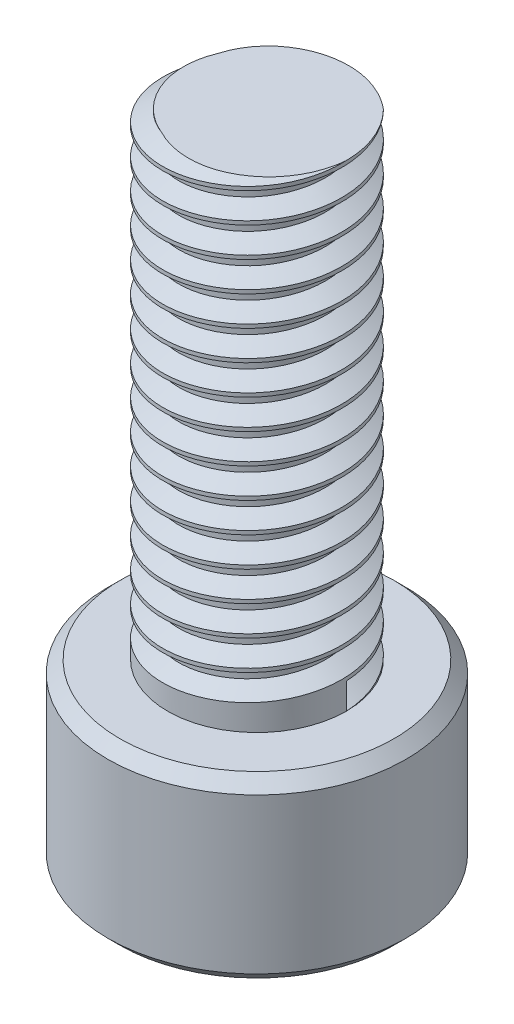
SolidWorks part; units mm, degrees
ref_plane "Front Plane" through (0, 0, 0) normal (0, 0, 1) x (1, 0, 0)
ref_plane "Top Plane" through (0, 0, 0) normal (0, 1, 0) x (1, 0, 0)
ref_plane "Right Plane" through (0, 0, 0) normal (1, 0, 0) x (0, 0, -1)
sketch "Sketch1" plane through (0, 0, 0) normal (0, 1, 0) x (1, 0, 0)
  circle A0 centre (0, 0) radius 2.5
extrude "Boss-Extrude1" add sketch "Sketch1" against normal blind 3
sketch "Sketch2" plane through (0, -3, 0) normal (0, -1, 0) x (1, 0, 0)
  line L1 (1.7321, 0) -> (0.866, 1.5)
  line L2 (0.866, 1.5) -> (-0.866, 1.5)
  line L3 (-0.866, 1.5) -> (-1.7321, 0)
  line L4 (-1.7321, 0) -> (-0.866, -1.5)
  line L5 (-0.866, -1.5) -> (0.866, -1.5)
  line L6 (0.866, -1.5) -> (1.7321, 0)
  circle A0 centre (0, 0) radius 1.5 construction
extrude "Cut-Extrude1" cut sketch "Sketch2" against normal blind 2
chamfer "Chamfer1" distance 0.2 angle 45 8 edges at (0, -3, 2.5) (0, -3, 1.5) (-1.299, -3, 0.75) (-1.299, -3, -0.75) (0, -3, -1.5) (1.299, -3, -0.75) (1.299, -3, 0.75) (0, 0, 2.5)
sketch "Sketch3" plane through (0, 0, 0) normal (0, 1, 0) x (1, 0, 0)
  circle A0 centre (0, 0) radius 1.5
extrude "Boss-Extrude2" add sketch "Sketch3" along normal blind 8
thread "Thread1" pitch 0.5 method cut profile "Thread Profile1" start angle 0, offset 0, length 40, pitch 0.5, diameter 3
ref_plane "Plane1" through (1.5, 0, 0) normal (0, 0, 1) x (1, 0, 0)
sketch "Thread Profile1" plane through (1.5, 0, 0) normal (0, 0, 1) x (1, 0, 0)
  line L0 (0, 0) -> (0, 0.5) construction
  line L11 (0, 0) -> (0, 0.4375)
  line L12 (0, 0.4375) -> (-0.2706, 0.2812)
  line L13 (-0.2706, 0.2812) -> (-0.2706, 0.1562)
  line L15 (-0.2706, 0.1562) -> (0, 0)
  line L17 (-0.2706, 0.2187) -> (0, 0.2187) construction
  point P2 (0, 0)
  dimension "Pitch" = 0.5
  dimension "Profile_Angle" = 60
  dimension "Profile_Land" = 0.125
  dimension "Profile_Height" = 0.2706
